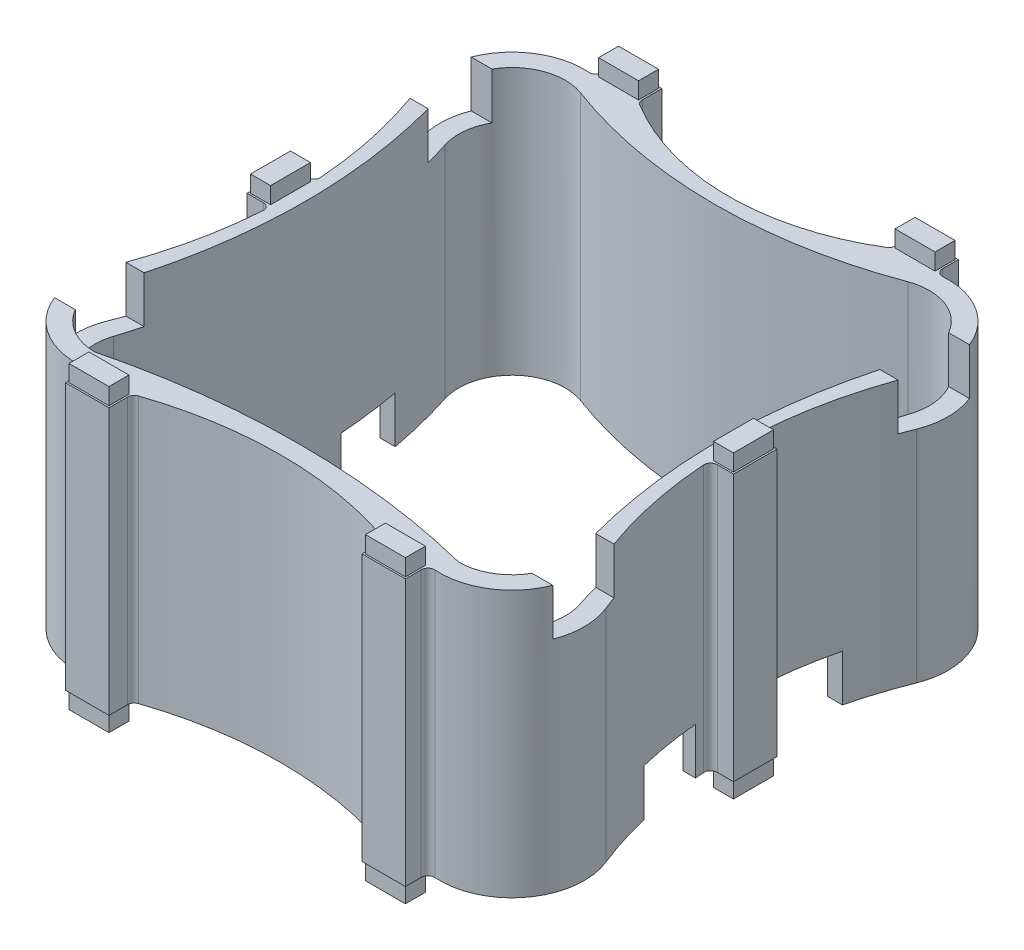
SolidWorks part; units mm, degrees
material "PA 类型 6"
ref_plane "前视基准面" through (0, 0, 0) normal (0, 0, 1) x (1, 0, 0)
ref_plane "上视基准面" through (0, 0, 0) normal (0, 1, 0) x (1, 0, 0)
ref_plane "右视基准面" through (0, 0, 0) normal (1, 0, 0) x (0, 0, -1)
sketch "参考面" plane through (0, 0, 0) normal (0, 1, 0) x (1, 0, 0)
  line L9 (-126.3139, 0) -> (116.7252, 0) construction
  line L10 (121.4406, 121.4406) -> (-121.4406, -121.4406) construction
  line L19 (-81.1154, 0) -> (102.0168, 0) construction
  line L20 (-108.2303, 108.2303) -> (124.7404, -124.7404) construction
  line L37 (0, 0) -> (86.2111, -62.636) construction
  line L56 (0, 63.4476) -> (0, -83.7805) construction
  line L92 (67.1165, -56.1685) -> (56.6027, -48.5298)
  line L94 (74.1596, -46.4745) -> (63.6458, -38.8359)
  line L111 (14.4084, 23.7665) -> (0, 9.3581)
  line L112 (21.4, 67.209) -> (28.6, 67.209)
  line L121 (4.0949, -56.1675) -> (4.0949, -53.2193)
  line L122 (-3.5956, -56.6668) -> (3.5956, -56.6668)
  line L123 (3.5956, -40.6902) -> (-3.5938, -40.6902)
  line L124 (4.0949, -41.1895) -> (4.0949, -44.1377)
  line L125 (-4.0949, -56.1675) -> (-4.0949, -53.2179)
  line L126 (-4.0949, -44.1363) -> (-4.0949, -41.1876)
  line L127 (-4.5418, -52.8684) -> (-4.4444, -52.8684)
  line L128 (-8.5359, -48.8743) -> (-8.5359, -48.4799)
  line L129 (8.5359, -48.8757) -> (8.5359, -48.4813)
  line L130 (4.4444, -52.8698) -> (4.5418, -52.8698)
  line L131 (4.5418, -44.4872) -> (4.4444, -44.4872)
  line L132 (-4.5418, -44.4858) -> (-4.4444, -44.4858)
  line L180 (-67.1165, 56.1685) -> (-56.6027, 48.5298)
  line L181 (-74.1596, 46.4745) -> (-63.6458, 38.8359)
  line L182 (-74.1596, -46.4745) -> (-63.6458, -38.8359)
  line L183 (-67.1165, -56.1685) -> (-56.6027, -48.5298)
  line L194 (-18.9731, -62.4083) -> (18.9712, -62.4083) construction
  line L200 (-11.2634, 52.145) -> (-6.2707, 52.145) construction
  line L201 (-11.2634, 50.8469) -> (-6.2707, 50.8469)
  line L202 (-11.2634, 53.4431) -> (-6.2707, 53.4431)
  line L206 (5.7117, 52.145) -> (0.719, 52.145) construction
  line L207 (5.7117, 53.4431) -> (0.719, 53.4431)
  line L208 (5.7117, 50.8469) -> (0.719, 50.8469)
  line L209 (74.1596, 46.4745) -> (63.6458, 38.8359)
  line L210 (43.9796, 31.9531) -> (60.1362, 43.6915) construction
  line L211 (67.1165, 56.1685) -> (56.6027, 48.5298)
  line L213 (-23.7665, 14.4084) -> (-9.3581, 0)
  line L214 (-58.8004, 0) -> (57.5251, 0) construction
  line L215 (-23.7665, -14.4084) -> (-9.3581, 0)
  line L241 (20.9, 49.291) -> (20.9, 66.709)
  line L242 (21.4, 48.791) -> (28.6, 48.791)
  line L243 (-14.4084, 23.7665) -> (0, 9.3581)
  line L244 (20.9, 58) -> (35.2287, 58) construction
  line L245 (25, 67.209) -> (25, 48.791) construction
  line L246 (29.1, 66.709) -> (29.1, 49.291)
  line L247 (23.7665, -14.4084) -> (9.3581, 0)
  line L248 (23.7665, 14.4084) -> (9.3581, 0)
  line L249 (-14.4084, -23.7665) -> (0, -9.3581)
  line L250 (14.4084, -23.7665) -> (0, -9.3581)
  line L255 (25.5, -41.5) -> (19, -41.5)
  line L256 (-25.5, 41.5) -> (-19, 41.5)
  line L257 (-25.5, 41.5) -> (-25.5, 38)
  line L258 (-25.5, 38) -> (-19, 38)
  line L259 (-19, 41.5) -> (-19, 38)
  line L260 (-36.5, 3.25) -> (-33, 3.25)
  line L261 (-36.5, 3.25) -> (-36.5, -3.25)
  line L262 (-36.5, -3.25) -> (-33, -3.25)
  line L263 (-33, 3.25) -> (-33, -3.25)
  line L264 (-25.5, -38) -> (-19, -38)
  line L265 (-25.5, -38) -> (-25.5, -41.5)
  line L266 (-25.5, -41.5) -> (-19, -41.5)
  line L267 (-19, -38) -> (-19, -41.5)
  line L268 (19, -38) -> (19, -41.5)
  line L269 (25.5, -38) -> (19, -38)
  line L270 (25.5, -38) -> (25.5, -41.5)
  line L271 (36.5, -3.25) -> (33, -3.25)
  line L272 (33, 3.25) -> (33, -3.25)
  line L273 (36.5, 3.25) -> (33, 3.25)
  line L274 (36.5, 3.25) -> (36.5, -3.25)
  line L275 (25.5, 38) -> (19, 38)
  line L276 (19, 41.5) -> (19, 38)
  line L277 (25.5, 41.5) -> (25.5, 38)
  line L278 (25.5, 41.5) -> (19, 41.5)
  circle A40 centre (9.9853, 9.9853) radius 1.0734
  circle A65 centre (12.7313, 12.7313) radius 1.0734
  circle A66 centre (15.2276, 15.2276) radius 1.5477
  circle A67 centre (-15.2276, 15.2276) radius 1.5477
  circle A68 centre (-12.7313, 12.7313) radius 1.0734
  circle A69 centre (-9.9853, 9.9853) radius 1.0734
  circle A70 centre (-9.9853, -9.9853) radius 1.0734
  circle A71 centre (-12.7313, -12.7313) radius 1.0734
  circle A72 centre (-15.2276, -15.2276) radius 1.5477
  circle A82 centre (15.2276, -15.2276) radius 1.5477
  circle A83 centre (12.7313, -12.7313) radius 1.0734
  circle A84 centre (9.9853, -9.9853) radius 1.0734
  circle A85 centre (27.9589, -27.9589) radius 3.1454
  circle A86 centre (-27.9589, -27.9589) radius 3.1454
  circle A101 centre (-27.9589, 27.9589) radius 3.1454
  circle A102 centre (27.9589, 27.9589) radius 3.1454
  circle A104 centre (43.9796, -31.9531) radius 1.5477
  circle A105 centre (60.1362, -43.6915) radius 1.5477
  circle A106 centre (-60.1362, -43.6915) radius 1.5477
  circle A113 centre (-23.2458, 52.145) radius 1.2981
  circle A114 centre (-43.9796, -31.9531) radius 1.5477
  circle A115 centre (60.1362, 43.6915) radius 1.5477
  circle A116 centre (43.9796, 31.9531) radius 1.5477
  circle A117 centre (-43.9796, 31.9531) radius 1.5477
  circle A118 centre (-60.1362, 43.6915) radius 1.5477
  arc A120 (67.1165, -56.1685) -> (74.1596, -46.4745) centre (70.638, -51.3215) ccw
  arc A121 (27.2174, -63.5024) -> (56.6027, -48.5298) centre (45.7245, -63.5024) cw
  arc A128 (-4.0949, -56.1675) -> (-3.5956, -56.6668) centre (-4.0949, -56.6668) ccw
  arc A129 (4.0949, -56.1675) -> (3.5956, -56.6668) centre (4.0949, -56.6668) cw
  arc A130 (4.0949, -41.1895) -> (3.5956, -40.6902) centre (4.0949, -40.6902) ccw
  arc A131 (-4.0949, -41.1876) -> (-3.5938, -40.6902) centre (-4.0931, -40.6884) cw
  arc A132 (8.5359, -48.4813) -> (4.5418, -44.4872) centre (4.5418, -48.4813) ccw
  arc A133 (-4.5418, -44.4858) -> (-8.5359, -48.4799) centre (-4.5418, -48.4799) ccw
  arc A134 (-4.5418, -52.8684) -> (-8.5359, -48.8743) centre (-4.5418, -48.8743) cw
  arc A135 (8.5359, -48.8757) -> (4.5418, -52.8698) centre (4.5418, -48.8757) cw
  arc A136 (4.0949, -44.1377) -> (4.4444, -44.4872) centre (4.4444, -44.1377) ccw
  arc A137 (4.0949, -53.2193) -> (4.4444, -52.8698) centre (4.4444, -53.2193) cw
  arc A138 (-4.0949, -44.1363) -> (-4.4444, -44.4858) centre (-4.4444, -44.1363) cw
  arc A139 (-4.0949, -53.2179) -> (-4.4444, -52.8684) centre (-4.4444, -53.2179) ccw
  arc A165 (-11.2634, 50.8469) -> (-11.2634, 53.4431) centre (-11.2634, 52.145) cw
  arc A166 (-6.2707, 53.4431) -> (-6.2707, 50.8469) centre (-6.2707, 52.145) cw
  arc A169 (5.7117, 53.4431) -> (5.7117, 50.8469) centre (5.7117, 52.145) cw
  arc A170 (0.719, 50.8469) -> (0.719, 53.4431) centre (0.719, 52.145) cw
  circle A175 centre (0, -38.4435) radius 1.5477
  circle A176 centre (0, -58.9135) radius 1.5477
  arc A177 (67.1165, 56.1685) -> (74.1596, 46.4745) centre (70.638, 51.3215) cw
  arc A178 (63.6458, 38.8359) -> (63.6458, -38.8359) centre (91.8617, 0) ccw
  circle A179 centre (43.9796, -31.9531) radius 5.9912 construction
  arc A180 (35.3497, 58.9683) -> (56.6027, 48.5298) centre (48.7329, 59.3617) ccw
  arc A181 (-67.1165, 56.1685) -> (-74.1596, 46.4745) centre (-70.638, 51.3215) ccw
  arc A182 (-35.3497, 58.9683) -> (-56.6027, 48.5298) centre (-48.7329, 59.3617) cw
  arc A183 (-63.6458, 38.8359) -> (-63.6458, -38.8359) centre (-91.8617, 0) cw
  arc A184 (-67.1165, -56.1685) -> (-74.1596, -46.4745) centre (-70.638, -51.3215) cw
  arc A185 (-27.2174, -63.5024) -> (-56.6027, -48.5298) centre (-45.7245, -63.5024) ccw
  arc A190 (-23.7665, 14.4084) -> (-29.7764, 19.3723) centre (-52.8107, -14.6358) ccw
  arc A191 (-23.7665, -14.4084) -> (-29.7764, -19.3723) centre (-52.8107, 14.6358) cw
  arc A192 (-29.7764, -19.3723) -> (-29.7764, 19.3723) centre (-91.8617, 0) ccw
  circle A202 centre (25, 69.659) radius 1.05
  arc A203 (20.9, 66.709) -> (21.4, 67.209) centre (20.9, 67.209) cw
  arc A204 (20.9, 49.291) -> (21.4, 48.791) centre (20.9, 48.791) ccw
  circle A205 centre (25, 46.341) radius 1.05
  arc A206 (29.1, 66.709) -> (28.6, 67.209) centre (29.1, 67.209) ccw
  arc A207 (29.1, 49.291) -> (28.6, 48.791) centre (29.1, 48.791) cw
  arc A208 (-14.4084, 23.7665) -> (-19.3723, 29.7764) centre (14.6358, 52.8107) cw
  arc A209 (-19.3723, 29.7764) -> (19.3723, 29.7764) centre (0, 91.8617) ccw
  arc A210 (14.4084, 23.7665) -> (19.3723, 29.7764) centre (-14.6358, 52.8107) ccw
  arc A211 (23.7665, 14.4084) -> (29.7764, 19.3723) centre (52.8107, -14.6358) cw
  arc A212 (29.7764, 19.3723) -> (29.7764, -19.3723) centre (91.8617, 0) ccw
  arc A213 (23.7665, -14.4084) -> (29.7764, -19.3723) centre (52.8107, 14.6358) ccw
  arc A214 (14.4084, -23.7665) -> (19.3723, -29.7764) centre (-14.6358, -52.8107) cw
  arc A215 (19.3723, -29.7764) -> (-19.3723, -29.7764) centre (0, -91.8617) ccw
  arc A216 (-14.4084, -23.7665) -> (-19.3723, -29.7764) centre (14.6358, -52.8107) ccw
  point P77 (0, 0)
  point P112 (-8.7671, 52.145)
  point P168 (3.2153, 52.145)
  point P443 (0, 0)
  dimension "D1" = 4
  dimension "D3" = 58
  dimension "D5" = 8.2
  dimension "D2" = 0.5
  dimension "D4" = 2.45
  dimension "D6" = 7.2
  dimension "D7" = 25
  dimension "D8" = 19
  dimension "D9" = 33
  dimension "D14" = 6.5
  dimension "D15" = 3.5
  dimension "D16" = 38
  dimension "D17" = 38
sketch "草图2" plane through (0, 0, 0) normal (0, 1, 0) x (1, 0, 0)
  line L1 (-61.3007, 0) -> (77.257, 0) construction
  line L8 (-33, 3.25) -> (-36.5, 3.25)
  line L9 (-36.5, 3.25) -> (-36.5, -3.25)
  line L31 (-36.5, -3.25) -> (-33, -3.25)
  line L33 (-25.5, 38) -> (-25.5, 41.5)
  line L56 (-25.5, 41.5) -> (-19, 41.5)
  line L57 (-19, 41.5) -> (-19, 38)
  line L58 (-25.5, -38) -> (-25.5, -41.5)
  line L59 (-25.5, -41.5) -> (-19, -41.5)
  line L60 (-19, -41.5) -> (-19, -38)
  line L61 (19, -41.5) -> (19, -38)
  line L62 (25.5, -41.5) -> (19, -41.5)
  line L63 (25.5, -38) -> (25.5, -41.5)
  line L64 (19, 41.5) -> (19, 38)
  line L65 (25.5, 41.5) -> (19, 41.5)
  line L66 (25.5, 38) -> (25.5, 41.5)
  line L67 (36.5, -3.25) -> (33, -3.25)
  line L68 (36.5, 3.25) -> (36.5, -3.25)
  line L69 (33, 3.25) -> (36.5, 3.25)
  line L74 (-126.3139, 0) -> (116.7252, 0) construction
  line L75 (0, 68.5797) -> (0, -68.5797) construction
  line L76 (0, 63.4476) -> (0, -83.7805) construction
  line L77 (-108.2303, 108.2303) -> (124.7404, -124.7404) construction
  arc A49 (-25.5, 38) -> (-37.3844, 23.3059) centre (-27.3145, 27.3145) ccw
  arc A52 (-24.5842, 34.8413) -> (-34.9442, 24.8864) centre (-27.3145, 27.3145) ccw
  arc A53 (-34.9442, -24.8864) -> (-34.9442, 24.8864) centre (-113.1442, 0) ccw
  arc A55 (-37.3844, -23.3059) -> (-33, -3.25) centre (-95.9302, 0) ccw
  arc A56 (-25.5, -38) -> (-37.3844, -23.3059) centre (-27.3145, -27.3145) cw
  arc A57 (-27.3357, -35.3212) -> (-34.9442, -24.8864) centre (-27.3145, -27.3145) cw
  arc A59 (-33, 3.25) -> (-37.3844, 23.3059) centre (-95.9302, 0) ccw
  arc A62 (33, 3.25) -> (37.3844, 23.3059) centre (95.9302, 0) cw
  arc A65 (27.3357, -35.3212) -> (34.9442, -24.8864) centre (27.3145, -27.3145) ccw
  arc A66 (25.5, -38) -> (37.3844, -23.3059) centre (27.3145, -27.3145) ccw
  arc A69 (37.3844, -23.3059) -> (33, -3.25) centre (95.9302, 0) cw
  arc A70 (34.9442, -24.8864) -> (34.9442, 24.8864) centre (113.1442, 0) cw
  arc A71 (24.5842, 34.8413) -> (34.9442, 24.8864) centre (27.3145, 27.3145) cw
  arc A72 (25.5, 38) -> (37.3844, 23.3059) centre (27.3145, 27.3145) cw
  arc A73 (-19, 38) -> (19, 38) centre (0, 67.9818) ccw
  arc A74 (-24.5842, 34.8413) -> (24.5842, 34.8413) centre (0, 100.6181) ccw
  arc A75 (-19, -38) -> (19, -38) centre (0, -91.6977) cw
  arc A76 (-27.3357, -35.3212) -> (27.3357, -35.3212) centre (0, -143.9681) cw
extrude "凸台-拉伸1" add sketch "草图2" against normal blind 40
sketch "草图5" plane through (0, 0, 0) normal (0, 1, 0) x (1, 0, 0)
  line L0 (-68.648, 0) -> (77.219, 0) construction
  line L1 (-126.3139, 0) -> (116.7252, 0) construction
  line L2 (0, 57.3258) -> (0, -69.9488) construction
  line L3 (0, 63.4476) -> (0, -83.7805) construction
  line L4 (-36.5, 3.25) -> (-33, 3.25) construction
  line L5 (-36.25, 3) -> (-33.25, 3)
  line L6 (-36.25, 3) -> (-36.25, -3)
  line L7 (-36.25, -3) -> (-33.25, -3)
  line L8 (-33.25, 3) -> (-33.25, -3)
  line L9 (-36.5, 3.25) -> (-36.5, -3.25) construction
  line L10 (-19, -38) -> (-19, -41.5) construction
  line L11 (-25.25, -38.25) -> (-19.25, -38.25)
  line L12 (-25.25, -38.25) -> (-25.25, -41.25)
  line L13 (-25.25, -41.25) -> (-19.25, -41.25)
  line L14 (-19.25, -38.25) -> (-19.25, -41.25)
  line L15 (-25.5, -41.5) -> (-19, -41.5) construction
  line L16 (-25.25, 41.25) -> (-19.25, 41.25)
  line L17 (-19.25, 38.25) -> (-19.25, 41.25)
  line L18 (-25.25, 38.25) -> (-19.25, 38.25)
  line L19 (-25.25, 38.25) -> (-25.25, 41.25)
  line L20 (25.25, 38.25) -> (25.25, 41.25)
  line L21 (25.25, 38.25) -> (19.25, 38.25)
  line L22 (19.25, 38.25) -> (19.25, 41.25)
  line L23 (25.25, 41.25) -> (19.25, 41.25)
  line L24 (19.25, -38.25) -> (19.25, -41.25)
  line L25 (25.25, -41.25) -> (19.25, -41.25)
  line L26 (25.25, -38.25) -> (25.25, -41.25)
  line L27 (25.25, -38.25) -> (19.25, -38.25)
  line L28 (33.25, 3) -> (33.25, -3)
  line L29 (36.25, -3) -> (33.25, -3)
  line L30 (36.25, 3) -> (36.25, -3)
  line L31 (36.25, 3) -> (33.25, 3)
  dimension "D1" = 0.25
  dimension "D2" = 0.25
  dimension "D3" = 3
  dimension "D4" = 0.25
  dimension "D5" = 0.25
extrude "凸台-拉伸3" add sketch "草图5" along normal blind 2.5
sketch "草图6" plane through (0, -40, 0) normal (0, -1, 0) x (1, 0, 0)
  line L0 (-44.389, 0) -> (42.3877, 0) construction
  line L1 (0, 51.2716) -> (0, -51.2716) construction
  line L2 (-25.25, 41.25) -> (-19.25, 41.25)
  line L3 (-36.25, 3) -> (-33.25, 3)
  line L4 (-36.25, 3) -> (-36.25, -3)
  line L5 (-36.25, -3) -> (-33.25, -3)
  line L6 (-33.25, 3) -> (-33.25, -3)
  line L7 (-25.25, -38.25) -> (-19.25, -38.25)
  line L8 (-25.25, -38.25) -> (-25.25, -41.25)
  line L9 (-25.25, -41.25) -> (-19.25, -41.25)
  line L10 (-19.25, -38.25) -> (-19.25, -41.25)
  line L11 (-19.25, 38.25) -> (-19.25, 41.25)
  line L12 (-25.25, 38.25) -> (-19.25, 38.25)
  line L13 (-25.25, 38.25) -> (-25.25, 41.25)
  line L14 (25.25, 38.25) -> (25.25, 41.25)
  line L15 (25.25, 38.25) -> (19.25, 38.25)
  line L16 (19.25, 38.25) -> (19.25, 41.25)
  line L17 (19.25, -38.25) -> (19.25, -41.25)
  line L18 (25.25, -41.25) -> (19.25, -41.25)
  line L19 (25.25, -38.25) -> (25.25, -41.25)
  line L20 (25.25, -38.25) -> (19.25, -38.25)
  line L21 (33.25, 3) -> (33.25, -3)
  line L22 (36.25, -3) -> (33.25, -3)
  line L23 (36.25, 3) -> (36.25, -3)
  line L24 (36.25, 3) -> (33.25, 3)
  line L25 (25.25, 41.25) -> (19.25, 41.25)
  line L26 (-36.5, 3.25) -> (-33, 3.25) construction
  line L27 (-36.5, -3.25) -> (-36.5, 3.25) construction
  line L28 (-25.5, -41.5) -> (-25.5, -38) construction
  line L29 (-19, -41.5) -> (-25.5, -41.5) construction
  dimension "D1" = 0.25
  dimension "D2" = 0.25
  dimension "D3" = 0.25
  dimension "D4" = 0.25
  dimension "D5" = 3
extrude "凸台-拉伸4" add sketch "草图6" along normal blind 2.5
fillet "圆角1" radius 1 12 edges at (33, -20, -3.25) (25.5, -20, -38) (-19, -20, -38) (19, -20, -38) (-25.5, -20, -38) (-33, -20, -3.25) (19, -20, 38) (33, -20, 3.25) (25.5, -20, 38) (-19, -20, 38) (-25.5, -20, 38) (-33, -20, 3.25)
sketch "草图7" plane through (0, 0, 0) normal (0, 1, 0) x (1, 0, 0)
  line L0 (-43.0337, 0) -> (42.851, 0) construction
  line L1 (0, 36.718) -> (0, -44.8375) construction
  line L2 (0, 0) -> (-41.2356, -29.9594) construction
  line L3 (-36.6337, -21.3237) -> (-33.8986, -21.3237)
  line L4 (-37.4219, -31.2746) -> (-34.2733, -31.2746)
  line L5 (36.6337, -21.3237) -> (33.8986, -21.3237)
  line L6 (37.4219, -31.2746) -> (34.2733, -31.2746)
  line L8 (-36.6337, 21.3237) -> (-33.8986, 21.3237)
  line L9 (-37.4219, 31.2746) -> (-34.2733, 31.2746)
  line L10 (37.4219, 31.2746) -> (34.2733, 31.2746)
  line L11 (36.6337, 21.3237) -> (33.8986, 21.3237)
  arc A0 (-34.9442, -24.8864) -> (-34.2733, -31.2746) centre (-27.2797, -27.3109) ccw
  arc A1 (-37.606, -23.8549) -> (-37.4219, -31.2746) centre (-27.2797, -27.3109) ccw
  arc A2 (-37.606, -23.8549) -> (-36.6337, -21.3237) centre (-95.9302, 0) ccw
  arc A3 (-34.9442, -24.8864) -> (-33.8986, -21.3237) centre (-113.1442, 0) ccw
  arc A4 (34.9442, -24.8864) -> (33.8986, -21.3237) centre (113.1442, 0) cw
  arc A5 (37.606, -23.8549) -> (36.6337, -21.3237) centre (95.9302, 0) cw
  arc A6 (37.606, -23.8549) -> (37.4219, -31.2746) centre (27.2797, -27.3109) cw
  arc A7 (34.9442, -24.8864) -> (34.2733, -31.2746) centre (27.2797, -27.3109) cw
  arc A12 (-34.9442, 24.8864) -> (-33.8986, 21.3237) centre (-113.1442, 0) cw
  arc A13 (-37.606, 23.8549) -> (-36.6337, 21.3237) centre (-95.9302, 0) cw
  arc A14 (-37.606, 23.8549) -> (-37.4219, 31.2746) centre (-27.2797, 27.3109) cw
  arc A15 (-34.9442, -24.8864) -> (-34.9442, 24.8864) centre (-113.1442, 0) ccw construction
  arc A16 (-34.9442, 24.8864) -> (-34.2733, 31.2746) centre (-27.2797, 27.3109) cw
  arc A17 (34.9442, 24.8864) -> (34.2733, 31.2746) centre (27.2797, 27.3109) ccw
  arc A18 (37.606, 23.8549) -> (37.4219, 31.2746) centre (27.2797, 27.3109) ccw
  arc A19 (37.606, 23.8549) -> (36.6337, 21.3237) centre (95.9302, 0) ccw
  arc A20 (34.9442, 24.8864) -> (33.8986, 21.3237) centre (113.1442, 0) ccw
  arc A22 (-34.9442, -24.8864) -> (-27.3357, -35.3212) centre (-27.3145, -27.3145) ccw construction
  dimension "D1" = 36
extrude "电调过线" cut sketch "草图7" against normal blind 7
sketch "草图8" plane through (0, -40, 0) normal (0, -1, 0) x (1, 0, 0)
  line L0 (-48.2566, 0) -> (46.2095, 0) construction
  line L1 (0, 0) -> (0, -36.4146) construction
  line L2 (-33.1672, -5.62) -> (-31.2724, -5.62)
  line L3 (-34.7046, -14.9062) -> (-32.4449, -14.9062)
  line L4 (-34.7046, 14.9062) -> (-32.4449, 14.9062)
  line L5 (-33.1672, 5.62) -> (-31.2724, 5.62)
  line L6 (33.1672, -5.62) -> (31.2724, -5.62)
  line L7 (34.7046, -14.9062) -> (32.4449, -14.9062)
  line L8 (33.1672, 5.62) -> (31.2724, 5.62)
  line L9 (34.7046, 14.9062) -> (32.4449, 14.9062)
  arc A0 (-37.3844, -23.3059) -> (-33.0643, -4.3185) centre (-95.9302, 0) ccw construction
  arc A1 (-34.9442, -24.8864) -> (-34.9442, 24.8864) centre (-113.1442, 0) ccw construction
  arc A2 (-33.1672, -5.62) -> (-34.7046, -14.9062) centre (-95.9302, 0) cw
  arc A3 (-31.2724, -5.62) -> (-32.4449, -14.9062) centre (-113.1442, 0) cw
  arc A4 (-33.1672, 5.62) -> (-34.7046, 14.9062) centre (-95.9302, 0) ccw
  arc A5 (-31.2724, 5.62) -> (-32.4449, 14.9062) centre (-113.1442, 0) ccw
  arc A6 (33.1672, -5.62) -> (34.7046, -14.9062) centre (95.9302, 0) ccw
  arc A7 (31.2724, -5.62) -> (32.4449, -14.9062) centre (113.1442, 0) ccw
  arc A8 (31.2724, 5.62) -> (32.4449, 14.9062) centre (113.1442, 0) cw
  arc A9 (33.1672, 5.62) -> (34.7046, 14.9062) centre (95.9302, 0) cw
extrude "电源过线" cut sketch "草图8" against normal blind 7
